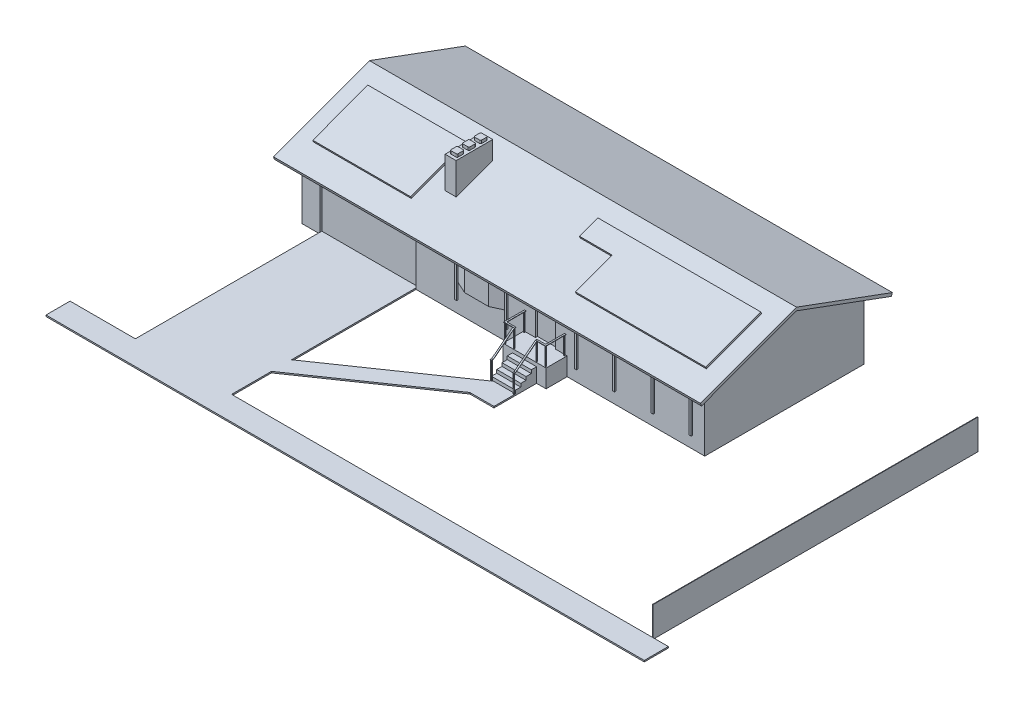
SolidWorks part; units mm, degrees
ref_plane "Front Plane" through (0, 0, 0) normal (0, 0, 1) x (1, 0, 0)
ref_plane "Top Plane" through (0, 0, 0) normal (0, 1, 0) x (1, 0, 0)
ref_plane "Right Plane" through (0, 0, 0) normal (1, 0, 0) x (0, 0, -1)
sketch "Sketch1" plane through (0, 0, 0) normal (0, 1, 0) x (1, 0, 0)
  line L1 (-10210.8, -4038.6) -> (10210.8, -4038.6)
  line L2 (-10210.8, -4038.6) -> (-10210.8, 4038.6)
  line L3 (-10210.8, 4038.6) -> (10210.8, 4038.6)
  line L4 (10210.8, -4038.6) -> (10210.8, 4038.6)
  line L5 (-10210.8, -4038.6) -> (10210.8, 4038.6) construction
  line L6 (-10210.8, 4038.6) -> (10210.8, -4038.6) construction
  point P0 (0, 0)
  dimension "D1" = 20421.6
  dimension "D2" = 8077.2
extrude "Boss-Extrude1" add sketch "Sketch1" along normal blind 3175
sketch "Sketch2" plane through (10210.8, 0, 0) normal (1, 0, 0) x (0, 0, -1)
  line L0 (-4809.5683, 2891.0202) -> (-4038.6, 3175)
  line L1 (4038.6, 3175) -> (4809.5683, 2891.0202)
  line L6 (-4862.2438, 3034.0274) -> (0, 4824.9946)
  line L7 (0, 4824.9946) -> (4862.2438, 3034.0274)
  line L8 (-4809.5683, 2891.0202) -> (-4862.2438, 3034.0274)
  line L9 (4809.5683, 2891.0202) -> (4862.2438, 3034.0274)
  line L10 (0, 0) -> (0, 7136.8719) construction
  line L11 (-4038.6, 3175) -> (4038.6, 3175)
  line L12 (-4038.6, 3175) -> (-4038.6, 0) construction
  line L13 (4038.6, 3175) -> (4038.6, 0) construction
  point P1 (0, 5113.5377)
  point P2 (0, 5113.5377)
  point P4 (0, 5113.5377)
  point P7 (0, 5189.3875)
  dimension "D1" = 5181.6
  dimension "D2" = 770.9683
  dimension "D3" = 770.9683
  dimension "D4" = 152.4
  dimension "D5" = 5181.6
  dimension "D6" = 152.4
extrude "Boss-Extrude2" add sketch "Sketch2" against normal up to surface (20421.6 mm away) up to face at (-10210.8, 1587.5, 0)
sketch "Sketch3" plane through (10210.8, 0, 0) normal (1, 0, 0) x (0, 0, -1)
  line L0 (-4862.2438, 3034.0274) -> (-4809.5683, 2891.0202)
  line L1 (-4809.5683, 2891.0202) -> (0, 4662.5849)
  line L2 (0, 4662.5849) -> (4809.5683, 2891.0202)
  line L3 (4809.5683, 2891.0202) -> (4862.2438, 3034.0274)
  line L4 (4862.2438, 3034.0274) -> (0, 4824.9946)
  line L5 (0, 4824.9946) -> (-4862.2438, 3034.0274)
extrude "Boss-Extrude3" add sketch "Sketch3" along normal blind 609.6
sketch "Sketch4" plane through (-10210.8, 0, 0) normal (-1, 0, 0) x (0, 0, 1)
  line L0 (-4862.2438, 3034.0274) -> (0, 4824.9946)
  line L1 (0, 4824.9946) -> (4862.2438, 3034.0274)
  line L2 (4862.2438, 3034.0274) -> (4809.5683, 2891.0202)
  line L3 (4809.5683, 2891.0202) -> (0, 4662.5849)
  line L4 (0, 4662.5849) -> (-4809.5683, 2891.0202)
  line L5 (-4809.5683, 2891.0202) -> (-4862.2438, 3034.0274)
extrude "Boss-Extrude4" add sketch "Sketch4" along normal blind 609.6
sketch "Sketch7" plane through (0, 0, 0) normal (0, 1, 0) x (1, 0, 0)
  line L0 (-10820.4, -4862.2438) -> (-10820.4, 0) construction
  line L1 (-4216.4, -914.4) -> (-3657.6, -914.4)
  line L2 (-4216.4, -914.4) -> (-4216.4, -2768.6)
  line L3 (-4216.4, -2768.6) -> (-3657.6, -2768.6)
  line L4 (-3657.6, -914.4) -> (-3657.6, -2768.6)
  line L5 (-10820.4, 0) -> (10820.4, 0) construction
  dimension "D1" = 6604
  dimension "D2" = 558.8
  dimension "D3" = 1854.2
  dimension "D4" = 914.4
extrude "Boss-Extrude5" add sketch "Sketch7" along normal blind 6165.342
sketch "Sketch8" plane through (-3657.6, 0, 0) normal (1, 0, 0) x (0, 0, -1)
  line L0 (-2768.6, 6165.342) -> (-914.4, 6165.342)
  line L1 (-914.4, 6165.342) -> (-914.4, 5402.5829)
  line L2 (-914.4, 6165.342) -> (-914.4, 4488.1829) construction
  line L3 (-914.4, 5402.5829) -> (-2768.6, 5402.5829)
  line L4 (-2768.6, 6165.342) -> (-2768.6, 3805.2037) construction
  line L5 (-2768.6, 5402.5829) -> (-2768.6, 6165.342)
  dimension "D1" = 914.4
extrude "Cut-Extrude1" cut sketch "Sketch8" against normal up to next
sketch "Sketch9" plane through (0, 4248.5676, 1564.9247) normal (0, 0.9384, 0.3456) x (1, 0, 0)
  line L0 (-8356.6, 753.3102) -> (-8356.6, -237.2898)
  line L1 (-10007.6, 753.3102) -> (-8356.6, 753.3102)
  line L2 (-10007.6, 753.3102) -> (-10007.6, -237.2898)
  line L3 (-10007.6, -237.2898) -> (-8356.6, -237.2898)
  line L4 (-8356.6, 753.3102) -> (-8356.6, -237.2898)
  line L5 (-8356.6, 753.3102) -> (-6705.6, 753.3102)
  line L6 (-6705.6, 753.3102) -> (-6705.6, -237.2898)
  line L7 (-8356.6, -237.2898) -> (-6705.6, -237.2898)
  line L8 (-6705.6, 753.3102) -> (-6705.6, -237.2898)
  line L9 (-6705.6, 753.3102) -> (-5054.6, 753.3102)
  line L10 (-5054.6, 753.3102) -> (-5054.6, -237.2898)
  line L11 (-6705.6, -237.2898) -> (-5054.6, -237.2898)
  line L12 (-8356.6, -237.2898) -> (-8356.6, -1227.8898)
  line L13 (-8356.6, -237.2898) -> (-6705.6, -237.2898)
  line L14 (-6705.6, -237.2898) -> (-6705.6, -1227.8898)
  line L15 (-8356.6, -1227.8898) -> (-6705.6, -1227.8898)
  line L16 (-6705.6, -237.2898) -> (-6705.6, -1227.8898)
  line L17 (-6705.6, -237.2898) -> (-5054.6, -237.2898)
  line L18 (-5054.6, -237.2898) -> (-5054.6, -1227.8898)
  line L19 (-6705.6, -1227.8898) -> (-5054.6, -1227.8898)
  line L20 (-8356.6, -1227.8898) -> (-8356.6, -2218.4898)
  line L21 (-8356.6, -1227.8898) -> (-6705.6, -1227.8898)
  line L22 (-6705.6, -1227.8898) -> (-6705.6, -2218.4898)
  line L23 (-8356.6, -2218.4898) -> (-6705.6, -2218.4898)
  line L24 (-6705.6, -1227.8898) -> (-6705.6, -2218.4898)
  line L25 (-6705.6, -1227.8898) -> (-5054.6, -1227.8898)
  line L26 (-5054.6, -1227.8898) -> (-5054.6, -2218.4898)
  line L27 (-6705.6, -2218.4898) -> (-5054.6, -2218.4898)
  line L28 (-10007.6, -237.2898) -> (-10007.6, -1227.8898)
  line L29 (-10007.6, -237.2898) -> (-8356.6, -237.2898)
  line L30 (-8356.6, -237.2898) -> (-8356.6, -1227.8898)
  line L31 (-10007.6, -1227.8898) -> (-8356.6, -1227.8898)
  line L32 (-10007.6, -1227.8898) -> (-10007.6, -2218.4898)
  line L33 (-10007.6, -1227.8898) -> (-8356.6, -1227.8898)
  line L34 (-8356.6, -1227.8898) -> (-8356.6, -2218.4898)
  line L35 (-10007.6, -2218.4898) -> (-8356.6, -2218.4898)
  line L36 (-10820.4, -3513.8898) -> (-10820.4, 1667.7102) construction
  line L37 (-10820.4, 1667.7102) -> (10820.4, 1667.7102) construction
  line L38 (6604, 753.3102) -> (6604, -237.2898)
  line L39 (8255, 753.3102) -> (9906, 753.3102)
  line L40 (8255, 753.3102) -> (8255, -237.2898)
  line L41 (8255, -237.2898) -> (9906, -237.2898)
  line L42 (9906, 753.3102) -> (9906, -237.2898)
  line L43 (6604, 753.3102) -> (8255, 753.3102)
  line L44 (8255, 753.3102) -> (8255, -237.2898)
  line L45 (6604, -237.2898) -> (8255, -237.2898)
  line L46 (4953, 753.3102) -> (4953, -237.2898)
  line L47 (4953, 753.3102) -> (6604, 753.3102)
  line L48 (6604, 753.3102) -> (6604, -237.2898)
  line L49 (4953, -237.2898) -> (6604, -237.2898)
  line L50 (3302, 753.3102) -> (3302, -237.2898)
  line L51 (3302, 753.3102) -> (4953, 753.3102)
  line L52 (4953, 753.3102) -> (4953, -237.2898)
  line L53 (3302, -237.2898) -> (4953, -237.2898)
  line L54 (6604, -237.2898) -> (6604, -1227.8898)
  line L55 (6604, -237.2898) -> (8255, -237.2898)
  line L56 (8255, -237.2898) -> (8255, -1227.8898)
  line L57 (6604, -1227.8898) -> (8255, -1227.8898)
  line L58 (4953, -237.2898) -> (4953, -1227.8898)
  line L59 (4953, -237.2898) -> (6604, -237.2898)
  line L60 (6604, -237.2898) -> (6604, -1227.8898)
  line L61 (4953, -1227.8898) -> (6604, -1227.8898)
  line L62 (3302, -237.2898) -> (3302, -1227.8898)
  line L63 (3302, -237.2898) -> (4953, -237.2898)
  line L64 (4953, -237.2898) -> (4953, -1227.8898)
  line L65 (3302, -1227.8898) -> (4953, -1227.8898)
  line L66 (6604, -1227.8898) -> (6604, -2218.4898)
  line L67 (6604, -1227.8898) -> (8255, -1227.8898)
  line L68 (8255, -1227.8898) -> (8255, -2218.4898)
  line L69 (6604, -2218.4898) -> (8255, -2218.4898)
  line L70 (4953, -1227.8898) -> (4953, -2218.4898)
  line L71 (4953, -1227.8898) -> (6604, -1227.8898)
  line L72 (6604, -1227.8898) -> (6604, -2218.4898)
  line L73 (4953, -2218.4898) -> (6604, -2218.4898)
  line L74 (3302, -1227.8898) -> (3302, -2218.4898)
  line L75 (3302, -1227.8898) -> (4953, -1227.8898)
  line L76 (4953, -1227.8898) -> (4953, -2218.4898)
  line L77 (3302, -2218.4898) -> (4953, -2218.4898)
  line L78 (8255, -237.2898) -> (8255, -1227.8898)
  line L79 (8255, -237.2898) -> (9906, -237.2898)
  line L80 (9906, -237.2898) -> (9906, -1227.8898)
  line L81 (8255, -1227.8898) -> (9906, -1227.8898)
  line L82 (8255, -1227.8898) -> (8255, -2218.4898)
  line L83 (8255, -1227.8898) -> (9906, -1227.8898)
  line L84 (9906, -1227.8898) -> (9906, -2218.4898)
  line L85 (8255, -2218.4898) -> (9906, -2218.4898)
  line L86 (10820.4, 1667.7102) -> (10820.4, -3513.8898) construction
  line L88 (3302, 753.3102) -> (1651, 753.3102)
  line L89 (3302, 753.3102) -> (3302, -237.2898)
  line L90 (3302, -237.2898) -> (1651, -237.2898)
  line L91 (1651, 753.3102) -> (1651, -237.2898)
  dimension "D1" = 1651
  dimension "D2" = 990.6
  dimension "D5" = 812.8
  dimension "D6" = 914.4
  dimension "D7" = 990.6
  dimension "D8" = 1651
  dimension "D11" = 914.4
  dimension "D12" = 914.4
  dimension "D13" = 1651
  dimension "D3" = 3
  dimension "D4" = 3
  dimension "D9" = 4
  dimension "D10" = 3
extrude "Boss-Extrude6" add sketch "Sketch9" along direction (0, 0.9384, 0.3456) on the side of the normal blind 101.6 contours L2 L3 L0 L1 | L0 L7 L6 L5 | L6 L11 L10 L9 | L28 L31 L12 L3 | L12 L15 L14 L7 | L14 L19 L18 L11 | L32 L35 L20 L31 | L20 L23 L22 L15 | L22 L27 L26 L19 | L88 L91 L90 L50 | L50 L53 L46 L51 | L62 L65 L58 L53 | L74 L77 L70 L65 | L70 L73 L66 L61 | L58 L61 L54 L49 | L46 L49 L38 L47 | L38 L45 L40 L43 | L54 L57 L56 L45 | L66 L69 L68 L57 | L68 L85 L84 L81 | L56 L81 L80 L41 | L42 L39 L40 L41 region at (-7531.1, 4337.7462, 1322.8163) region at (-9182.1, 4337.7462, 1322.8163) region at (-9182.1, 3995.3554, 2252.3629) region at (-7531.1, 3995.3554, 2252.3629) region at (-5880.1, 4337.7462, 1322.8163) region at (-5880.1, 3995.3554, 2252.3629) region at (-7531.1, 3652.9646, 3181.9096) region at (-9182.1, 3652.9646, 3181.9096) region at (-5880.1, 3652.9646, 3181.9096) region at (7429.5, 4337.7462, 1322.8163) region at (5778.5, 4337.7462, 1322.8163) region at (5778.5, 3995.3554, 2252.3629) region at (7429.5, 3995.3554, 2252.3629) region at (9080.5, 4337.7462, 1322.8163) region at (4127.5, 4337.7462, 1322.8163) region at (9080.5, 3995.3554, 2252.3629) region at (4127.5, 3995.3554, 2252.3629) region at (5778.5, 3652.9646, 3181.9096) region at (7429.5, 3652.9646, 3181.9096) region at (2476.5, 4337.7462, 1322.8163) region at (9080.5, 3652.9646, 3181.9096) region at (4127.5, 3652.9646, 3181.9096)
sketch "Sketch10" plane through (0, 0, 4038.6) normal (0, 0, 1) x (1, 0, 0)
  line L0 (-10210.8, 0) -> (10210.8, 0) construction
  line L1 (-9296.4, 0) -> (-4419.6, 0)
  line L2 (-9296.4, 0) -> (-9296.4, 2438.4)
  line L3 (-9296.4, 2438.4) -> (-4419.6, 2438.4)
  line L4 (-4419.6, 0) -> (-4419.6, 2438.4)
  line L5 (-10210.8, 3175) -> (-10210.8, 0) construction
  line L6 (-2286, 1371.6) -> (152.4, 1371.6)
  line L7 (-2286, 1371.6) -> (-2286, 3175)
  line L8 (-2286, 3175) -> (152.4, 3175)
  line L9 (152.4, 1371.6) -> (152.4, 3175)
  line L10 (1054.1, 914.4) -> (3238.5, 914.4)
  line L11 (1054.1, 914.4) -> (1054.1, 0)
  line L12 (1054.1, 0) -> (3238.5, 0)
  line L13 (3238.5, 914.4) -> (3238.5, 0)
  line L14 (1638.3, 2971.8) -> (2654.3, 2971.8)
  line L15 (1638.3, 2971.8) -> (1638.3, 914.4)
  line L16 (1638.3, 914.4) -> (2654.3, 914.4)
  line L17 (2654.3, 2971.8) -> (2654.3, 914.4)
  line L18 (3784.6, 2997.2) -> (5613.4, 2997.2)
  line L19 (3784.6, 2997.2) -> (3784.6, 2133.6)
  line L20 (3784.6, 2133.6) -> (5613.4, 2133.6)
  line L21 (5613.4, 2997.2) -> (5613.4, 2133.6)
  line L22 (7670.8, 2997.2) -> (9499.6, 2997.2)
  line L23 (7670.8, 2997.2) -> (7670.8, 2133.6)
  line L24 (7670.8, 2133.6) -> (9499.6, 2133.6)
  line L25 (9499.6, 2997.2) -> (9499.6, 2133.6)
  line L26 (10210.8, 3175) -> (10210.8, 0) construction
  line L27 (-10210.8, 3175) -> (10210.8, 3175) construction
  point P30 (2146.3, 914.4)
  point P31 (2146.3, 914.4)
  line M23 (-10210.8, 0) -> (10210.8, 0)
  line M25 (10210.8, 3175) -> (-10210.8, 3175)
  dimension "D1" = 914.4
  dimension "D2" = 4876.8
  dimension "D3" = 2438.4
  dimension "D4" = 2133.6
  dimension "D5" = 711.2
  dimension "D6" = 1828.8
  dimension "D7" = 2057.4
  dimension "D8" = 1828.8
  dimension "D9" = 546.1
  dimension "D10" = 2184.4
  dimension "D11" = 1016
  dimension "D12" = 914.4
  dimension "D13" = 2057.4
  dimension "D14" = 863.6
  dimension "D15" = 863.6
  dimension "D16" = 2133.6
  dimension "D17" = 2133.6
  dimension "D18" = 1371.6
  dimension "D19" = 2438.4
extrude "Cut-Extrude2" cut sketch "Sketch10" against normal blind 101.6 contours L4 L3 L2 M23 | L21 L18 L19 L20 | L25 L22 L23 L24 region at (-6858, 1219.2, 4038.6) region at (4699, 2565.4, 4038.6) region at (8585.2, 2565.4, 4038.6)
extrude "Boss-Extrude7" add sketch "Sketch10<3>" along normal blind 1066.8 contours L13 L10 L11 M23 region at (2146.3, 457.2, 4038.6)
sketch "Sketch10<3>" plane through (0, 0, 4038.6) normal (0, 0, 1) x (1, 0, 0) same geometry as "Sketch10"
extrude "Boss-Extrude8" add sketch "Sketch10<4>" along normal blind 279.4 contours L6 L9 L7 M25 region at (-1066.8, 2273.3, 4038.6)
sketch "Sketch10<4>" plane through (0, 0, 4038.6) normal (0, 0, 1) x (1, 0, 0) same geometry as "Sketch10"
sketch "Sketch11" plane through (0, 1371.6, 0) normal (0, -1, 0) x (1, 0, 0)
  line L0 (-1676.4, 4318) -> (-2286, 4038.6)
  line L1 (-2286, 4318) -> (152.4, 4318) construction
  line L2 (-2286, 4318) -> (-2286, 4038.6) construction
  line L3 (-2286, 4038.6) -> (-2286, 4318)
  line L4 (-2286, 4318) -> (-1676.4, 4318)
  line L10 (152.4, 4038.6) -> (-457.2, 4318)
  line L11 (-457.2, 4318) -> (152.4, 4318)
  line L12 (152.4, 4318) -> (152.4, 4038.6)
  line L13 (-1066.8, 4318) -> (-1066.8, 3614.0331) construction
  line L15 (152.4, 4318) -> (-2286, 4318) construction
  point P15 (-1066.8, 4318)
  point P16 (-1066.8, 4318)
  dimension "D1" = 1219.2
  dimension "D2" = 609.6
extrude "Cut-Extrude3" cut sketch "Sketch11" against normal up to surface (1700.4853 mm away) up to face at (-355.6, 3606.3792, 2867.4614)
extrude "Cut-Extrude4" cut sketch "Sketch10<5>" against normal blind 101.6 contours L17 L14 L15 L10 region at (2146.3, 1943.1, 4038.6)
sketch "Sketch10<5>" plane through (0, 0, 4038.6) normal (0, 0, 1) x (1, 0, 0) same geometry as "Sketch10"
sketch "Sketch12" plane through (0, 0, 5105.4) normal (0, 0, 1) x (1, 0, 0)
  line L0 (1054.1, 0) -> (3238.5, 0) construction
  line L1 (1536.7, 0) -> (2755.9, 0)
  line L2 (1536.7, 0) -> (1536.7, 730.25)
  line L3 (1536.7, 730.25) -> (2755.9, 730.25)
  line L4 (2755.9, 0) -> (2755.9, 730.25)
  line L5 (2146.3, -952.0203) -> (2146.3, 3746.1665) construction
  line L6 (1054.1, 914.4) -> (3238.5, 914.4) construction
  line L7 (1638.3, 914.4) -> (2654.3, 914.4) construction
  point P8 (2146.3, 730.25)
  point P11 (2146.3, 914.4)
  dimension "D1" = 1219.2
  dimension "D2" = 184.15
extrude "Boss-Extrude9" add sketch "Sketch12" along normal blind 1066.8
sketch "Sketch13" plane through (2755.9, 0, 0) normal (1, 0, 0) x (0, 0, -1)
  line L0 (-5372.1, 730.25) -> (-5372.1, 565.15)
  line L1 (-6172.2, 730.25) -> (-5105.4, 730.25) construction
  line L2 (-5372.1, 565.15) -> (-5638.8, 565.15)
  line L3 (-5638.8, 565.15) -> (-5638.8, 400.05)
  line L4 (-5638.8, 400.05) -> (-5905.5, 400.05)
  line L5 (-5905.5, 400.05) -> (-5905.5, 234.95)
  line L6 (-5905.5, 234.95) -> (-6172.2, 234.95)
  line L7 (-6172.2, 0) -> (-6172.2, 730.25) construction
  line L8 (-6172.2, 234.95) -> (-6172.2, 730.25)
  line L9 (-6172.2, 730.25) -> (-5372.1, 730.25)
  line L10 (-5105.4, 0) -> (-5105.4, 730.25) construction
  line L11 (-6172.2, 0) -> (-5105.4, 0) construction
  dimension "D1" = 266.7
  dimension "D2" = 266.7
  dimension "D3" = 266.7
  dimension "D4" = 165.1
  dimension "D5" = 165.1
  dimension "D6" = 165.1
  dimension "D7" = 234.95
extrude "Cut-Extrude5" cut sketch "Sketch13" against normal up to next
sketch "Sketch14" plane through (0, 0, 6172.2) normal (0, 0, 1) x (1, 0, 0)
  line L0 (1536.7, 234.95) -> (1536.7, 0) construction
  line L5 (1536.7, 0) -> (2755.9, 0)
  line L6 (1536.7, 0) -> (1536.7, 69.85)
  line L7 (1536.7, 69.85) -> (2755.9, 69.85)
  line L8 (2755.9, 0) -> (2755.9, 69.85)
  line L9 (2755.9, 0) -> (2755.9, 234.95) construction
  line L10 (1536.7, 234.95) -> (2755.9, 234.95) construction
  dimension "D1" = 165.1
extrude "Boss-Extrude10" add sketch "Sketch14" along normal blind 1092.2
sketch "Sketch15" plane through (0, 0, 3937) normal (0, 0, 1) x (1, 0, 0)
  line L0 (-4419.6, 0) -> (-4419.6, 2438.4) construction
  line L1 (-9296.4, 0) -> (-4419.6, 0)
  line L2 (-9296.4, 0) -> (-9296.4, 69.85)
  line L3 (-9296.4, 69.85) -> (-4419.6, 69.85)
  line L4 (-4419.6, 0) -> (-4419.6, 69.85)
  dimension "D1" = 69.85
extrude "Boss-Extrude11" add sketch "Sketch15" along normal blind 9448.8
sketch "Sketch16" plane through (0, 0, 0) normal (0, 1, 0) x (1, 0, 0)
  line L0 (1536.7, -7264.4) -> (-4419.6, -11364.6438)
  line L1 (-4419.6, -13385.8) -> (-4419.6, -4038.6) construction
  line L2 (-4419.6, -11364.6438) -> (-4419.6, -10348.6438)
  line L3 (-4419.6, -10348.6438) -> (1536.7, -6248.4)
  line L4 (1536.7, -6248.4) -> (1536.7, -7264.4)
  line L5 (-10820.4, -4862.2438) -> (10820.4, -4862.2438) construction
  point P10 (0, 0)
  point P11 (1536.7, -6375.7175)
  dimension "D1" = 5486.4
  dimension "D2" = 1016
  dimension "D3" = 1016
extrude "Boss-Extrude12" add sketch "Sketch16" along normal blind 69.85
sketch "Sketch17" plane through (0, 0, 13385.8) normal (0, 0, 1) x (1, 0, 0)
  line L0 (-4419.6, 69.85) -> (-9296.4, 69.85) construction
  line L1 (-12605.8014, 0) -> (17713.7666, 0)
  line L2 (-12605.8014, 0) -> (-12605.8014, 69.85)
  line L3 (-12605.8014, 69.85) -> (17713.7666, 69.85)
  line L4 (17713.7666, 0) -> (17713.7666, 69.85)
  line L5 (-9296.4, 0) -> (-4419.6, 0) construction
extrude "Boss-Extrude13" add sketch "Sketch17" along normal blind 1219.2
sketch "Sketch18" plane through (0, 0, 4038.6) normal (0, 0, 1) x (1, 0, 0)
  line L0 (3784.6, 2997.2) -> (3784.6, 2133.6) construction
  line L1 (3683, 609.6) -> (3784.6, 609.6)
  line L2 (3683, 609.6) -> (3683, 3175)
  line L3 (3683, 3175) -> (3784.6, 3175)
  line L4 (3784.6, 609.6) -> (3784.6, 3175)
  line L5 (5613.4, 609.6) -> (5715, 609.6)
  line L6 (5613.4, 609.6) -> (5613.4, 3175)
  line L7 (5613.4, 3175) -> (5715, 3175)
  line L8 (5715, 609.6) -> (5715, 3175)
  line L9 (7569.2, 609.6) -> (7670.8, 609.6)
  line L10 (7569.2, 609.6) -> (7569.2, 3175)
  line L11 (7569.2, 3175) -> (7670.8, 3175)
  line L12 (7670.8, 609.6) -> (7670.8, 3175)
  line L13 (9499.6, 609.6) -> (9601.2, 609.6)
  line L14 (9499.6, 609.6) -> (9499.6, 3175)
  line L15 (9499.6, 3175) -> (9601.2, 3175)
  line L16 (9601.2, 609.6) -> (9601.2, 3175)
  line L17 (5613.4, 2997.2) -> (5613.4, 2133.6) construction
  line L18 (7670.8, 2997.2) -> (7670.8, 2133.6) construction
  line L19 (9499.6, 2997.2) -> (9499.6, 2133.6) construction
  line L20 (3238.5, 0) -> (10210.8, 0) construction
  line L21 (152.4, 3175) -> (10210.8, 3175) construction
  line L22 (-10210.8, 3175) -> (-2286, 3175) construction
  line L23 (-2387.6, 3175) -> (-2286, 3175)
  line L24 (-2387.6, 3175) -> (-2387.6, 609.6)
  line L25 (-2387.6, 609.6) -> (-2286, 609.6)
  line L26 (-2286, 3175) -> (-2286, 609.6)
  line L27 (152.4, 3175) -> (254, 3175)
  line L28 (152.4, 3175) -> (152.4, 609.6)
  line L29 (152.4, 609.6) -> (254, 609.6)
  line L30 (254, 3175) -> (254, 609.6)
  line L31 (-2286, 1371.6) -> (-2286, 3175) construction
  line L32 (152.4, 1371.6) -> (152.4, 3175) construction
  dimension "D1" = 101.6
  dimension "D2" = 609.6
extrude "Boss-Extrude14" add sketch "Sketch18" along normal blind 76.2
sketch "Sketch19" plane through (0, 914.4, 0) normal (0, 1, 0) x (1, 0, 0)
  line L0 (1054.1, -5105.4) -> (3238.5, -5105.4) construction
  line L1 (1092.2, -5067.3) -> (1130.3, -5067.3)
  line L2 (1092.2, -5067.3) -> (1092.2, -5029.2)
  line L3 (1092.2, -5029.2) -> (1130.3, -5029.2)
  line L4 (1130.3, -5067.3) -> (1130.3, -5029.2)
  line L5 (3176.5995, -5067.3) -> (3138.4995, -5067.3)
  line L6 (3176.5995, -5067.3) -> (3176.5995, -5029.2)
  line L7 (3176.5995, -5029.2) -> (3138.4995, -5029.2)
  line L8 (3138.4995, -5067.3) -> (3138.4995, -5029.2)
  line L9 (3138.4995, -4076.7) -> (3176.5995, -4076.7)
  line L10 (3138.4995, -4076.7) -> (3138.4995, -4114.8)
  line L11 (3138.4995, -4114.8) -> (3176.5995, -4114.8)
  line L12 (3176.5995, -4076.7) -> (3176.5995, -4114.8)
  line L13 (1092.2, -4076.7) -> (1130.3, -4076.7)
  line L14 (1092.2, -4076.7) -> (1092.2, -4114.8)
  line L15 (1092.2, -4114.8) -> (1130.3, -4114.8)
  line L16 (1130.3, -4076.7) -> (1130.3, -4114.8)
  line L17 (1557.7366, -5029.2) -> (1595.8366, -5029.2)
  line L18 (1557.7366, -5029.2) -> (1557.7366, -5067.3)
  line L19 (1557.7366, -5067.3) -> (1595.8366, -5067.3)
  line L20 (1595.8366, -5029.2) -> (1595.8366, -5067.3)
  line L21 (2734.3851, -5067.3) -> (2696.2851, -5067.3)
  line L22 (2734.3851, -5067.3) -> (2734.3851, -5029.2)
  line L23 (2734.3851, -5029.2) -> (2696.2851, -5029.2)
  line L24 (2696.2851, -5067.3) -> (2696.2851, -5029.2)
  line L25 (1054.1, -5105.4) -> (1054.1, -4038.6) construction
  line L26 (1054.1, -4038.6) -> (1638.3, -4038.6) construction
  dimension "D1" = 38.1
  dimension "D2" = 38.1
  dimension "D3" = 38.1
  dimension "D4" = 38.1
  dimension "D5" = 38.1
  dimension "D6" = 38.1
  dimension "D7" = 38.1
extrude "Boss-Extrude15" add sketch "Sketch19" along normal blind 914.4
sketch "Sketch20" plane through (0, 1828.8, 0) normal (0, 1, 0) x (1, 0, 0)
  line L0 (1130.3, -4114.8) -> (1130.3, -4076.7) construction
  line L1 (1073.15, -4022.2988) -> (1149.35, -4022.2988)
  line L2 (1073.15, -4022.2988) -> (1073.15, -5086.35)
  line L3 (1073.15, -5086.35) -> (1149.35, -5086.35)
  line L4 (1149.35, -4022.2988) -> (1149.35, -5086.35)
  line L5 (1149.35, -5086.35) -> (1614.8866, -5086.35)
  line L6 (1149.35, -5086.35) -> (1149.35, -5010.15)
  line L7 (1149.35, -5010.15) -> (1614.8866, -5010.15)
  line L8 (1614.8866, -5086.35) -> (1614.8866, -5010.15)
  line L9 (3119.4495, -4057.65) -> (3195.6495, -4057.65)
  line L10 (3119.4495, -4057.65) -> (3119.4495, -5086.35)
  line L11 (3119.4495, -5086.35) -> (3195.6495, -5086.35)
  line L12 (3195.6495, -4057.65) -> (3195.6495, -5086.35)
  line L13 (3119.4495, -5086.35) -> (2677.2351, -5086.35)
  line L14 (3119.4495, -5086.35) -> (3119.4495, -5010.15)
  line L15 (3119.4495, -5010.15) -> (2677.2351, -5010.15)
  line L16 (2677.2351, -5086.35) -> (2677.2351, -5010.15)
  line L17 (1092.2, -5067.3) -> (1130.3, -5067.3) construction
  line L18 (1595.8366, -5067.3) -> (1595.8366, -5029.2) construction
  line L19 (2696.2851, -5029.2) -> (2696.2851, -5067.3) construction
  line L20 (3176.5995, -5067.3) -> (3176.5995, -5029.2) construction
  line L21 (3176.5995, -4076.7) -> (3138.4995, -4076.7) construction
  line L22 (2696.2851, -5067.3) -> (2734.3851, -5067.3) construction
  line M11 (1092.2, -4076.7) -> (1092.2, -4114.8)
  line M12 (1092.2, -4114.8) -> (1130.3, -4114.8)
  line M13 (1130.3, -4114.8) -> (1130.3, -4076.7)
  line M14 (1130.3, -4076.7) -> (1092.2, -4076.7)
  dimension "D1" = 76.2
  dimension "D2" = 76.2
  dimension "D3" = 76.2
  dimension "D4" = 76.2
  dimension "D5" = 19.05
  dimension "D6" = 19.05
  dimension "D7" = 19.05
  dimension "D8" = 19.05
  dimension "D9" = 19.05
  dimension "D10" = 19.05
  dimension "D11" = 19.05
extrude "Boss-Extrude17" add sketch "Sketch20" along normal blind 19.05 contours L4 L1 L2 L3 M11 M14 M13 M12 | L5 L8 L7 L4 | L16 L13 L10 L15 | L12 L9 L10 L11 | M14 M11 M12 M13 region at (1111.25, 1828.8, 4562.6841) region at (1382.1183, 1828.8, 5048.25) region at (3157.5495, 1828.8, 4572) region at (2898.3423, 1828.8, 5048.25) region at (1111.25, 1828.8, 4095.75)
sketch "Sketch21" plane through (0, 69.85, 0) normal (0, 1, 0) x (1, 0, 0)
  line L0 (2734.3851, -5067.3) -> (2734.3851, -5029.2) construction
  line L1 (1557.7366, -6229.35) -> (1595.8366, -6229.35)
  line L2 (1557.7366, -6229.35) -> (1557.7366, -6191.25)
  line L3 (1557.7366, -6191.25) -> (1595.8366, -6191.25)
  line L4 (1595.8366, -6229.35) -> (1595.8366, -6191.25)
  line L5 (2696.2851, -6229.35) -> (2734.3851, -6229.35)
  line L6 (2696.2851, -6229.35) -> (2696.2851, -6191.25)
  line L7 (2696.2851, -6191.25) -> (2734.3851, -6191.25)
  line L8 (2734.3851, -6229.35) -> (2734.3851, -6191.25)
  line L9 (2696.2851, -5029.2) -> (2696.2851, -5067.3) construction
  line L10 (1557.7366, -5029.2) -> (1557.7366, -5067.3) construction
  line L11 (1595.8366, -5067.3) -> (1595.8366, -5029.2) construction
  line L12 (2755.9, -6172.2) -> (1536.7, -6172.2) construction
  dimension "D1" = 38.1
  dimension "D2" = 19.05
extrude "Boss-Extrude18" add sketch "Sketch21" along normal blind 914.4
sketch "Sketch22" plane through (0, 984.25, 0) normal (0, 1, 0) x (1, 0, 0)
  line L0 (1557.7366, -6191.25) -> (1557.7366, -6229.35) construction
  line L1 (1538.6866, -6172.2) -> (1614.8866, -6172.2)
  line L2 (1538.6866, -6172.2) -> (1538.6866, -6248.4)
  line L3 (1538.6866, -6248.4) -> (1614.8866, -6248.4)
  line L4 (1614.8866, -6172.2) -> (1614.8866, -6248.4)
  line L5 (2677.2351, -6172.2) -> (2753.4351, -6172.2)
  line L6 (2677.2351, -6172.2) -> (2677.2351, -6248.4)
  line L7 (2677.2351, -6248.4) -> (2753.4351, -6248.4)
  line L8 (2753.4351, -6172.2) -> (2753.4351, -6248.4)
  line L9 (1557.7366, -6229.35) -> (1595.8366, -6229.35) construction
  line L10 (2734.3851, -6229.35) -> (2734.3851, -6191.25) construction
  dimension "D1" = 76.2
  dimension "D2" = 19.05
  dimension "D3" = 19.05
  dimension "D4" = 19.05
extrude "Boss-Extrude19" add sketch "Sketch22" along normal blind 19.05
sketch "Sketch23" plane through (0, 0, 5086.35) normal (0, 0, 1) x (1, 0, 0)
  line L0 (1073.15, 1847.85) -> (1614.8866, 1847.85) construction
  line L1 (1614.8866, 1828.8) -> (1538.6866, 1828.8)
  line L2 (1614.8866, 1828.8) -> (1614.8866, 1847.85)
  line L3 (1614.8866, 1847.85) -> (1538.6866, 1847.85)
  line L4 (1538.6866, 1828.8) -> (1538.6866, 1847.85)
  line L5 (3195.6495, 1847.85) -> (2677.2351, 1847.85) construction
  line L6 (2677.2351, 1828.8) -> (2753.4351, 1828.8)
  line L7 (2677.2351, 1828.8) -> (2677.2351, 1847.85)
  line L8 (2677.2351, 1847.85) -> (2753.4351, 1847.85)
  line L9 (2753.4351, 1828.8) -> (2753.4351, 1847.85)
  dimension "D1" = 76.2
  dimension "D2" = 76.2
sketch3d "3DSketch1"
  line L0 (1538.6866, 1847.85, 5086.35) -> (1538.6866, 1003.3, 6172.2)
  line L1 (2677.2351, 1847.85, 5086.35) -> (2677.2351, 1003.3, 6172.2)
  line L2 (2753.4351, 1847.85, 5086.35) -> (2753.4351, 1003.3, 6172.2)
loft "Loft1" add section "Sketch23" section face at (1576.7866, 993.775, 6172.2) connector at (1538.6866, 1847.85, 5086.35) connector at (1538.6866, 1003.3, 6172.2)
loft "Loft3" add section face at (2715.3351, 993.775, 6172.2) section "Sketch23<5>" connector at (2753.4351, 984.25, 6172.2) connector at (2753.4351, 1828.8, 5086.35)
sketch "Sketch23<5>" plane through (0, 0, 5086.35) normal (0, 0, 1) x (1, 0, 0) same geometry as "Sketch23"
sketch "Sketch24" plane through (0, 5402.5829, 0) normal (0, 1, 0) x (1, 0, 0)
  line L0 (-3937, -914.4) -> (-3937, -2768.6) construction
  line L1 (-4064, -1066.8) -> (-3810, -1066.8)
  line L2 (-4114.8, -1117.6) -> (-4114.8, -1371.6)
  line L3 (-4064, -1422.4) -> (-3810, -1422.4)
  line L4 (-3759.2, -1117.6) -> (-3759.2, -1371.6)
  line L5 (-4064, -1663.7) -> (-3810, -1663.7)
  line L6 (-4114.8, -1714.5) -> (-4114.8, -1968.5)
  line L7 (-4064, -2019.3) -> (-3810, -2019.3)
  line L8 (-3759.2, -1714.5) -> (-3759.2, -1968.5)
  line L9 (-4064, -2260.6) -> (-3810, -2260.6)
  line L10 (-4114.8, -2311.4) -> (-4114.8, -2565.4)
  line L11 (-4064, -2616.2) -> (-3810, -2616.2)
  line L12 (-3759.2, -2311.4) -> (-3759.2, -2565.4)
  line L13 (-4216.4, -914.4) -> (-3657.6, -914.4) construction
  line L14 (-4216.4, -2768.6) -> (-3657.6, -2768.6) construction
  line L15 (-4609.6328, -1841.5) -> (-3072.9217, -1841.5) construction
  arc A0 (-3810, -2616.2) -> (-3759.2, -2565.4) centre (-3810, -2565.4) ccw
  arc A1 (-4114.8, -2565.4) -> (-4064, -2616.2) centre (-4064, -2565.4) ccw
  arc A2 (-4064, -2260.6) -> (-4114.8, -2311.4) centre (-4064, -2311.4) ccw
  arc A3 (-3810, -2260.6) -> (-3759.2, -2311.4) centre (-3810, -2311.4) cw
  arc A4 (-4114.8, -1968.5) -> (-4064, -2019.3) centre (-4064, -1968.5) ccw
  arc A5 (-3810, -2019.3) -> (-3759.2, -1968.5) centre (-3810, -1968.5) ccw
  arc A6 (-3810, -1663.7) -> (-3759.2, -1714.5) centre (-3810, -1714.5) cw
  arc A7 (-4064, -1663.7) -> (-4114.8, -1714.5) centre (-4064, -1714.5) ccw
  arc A8 (-4114.8, -1371.6) -> (-4064, -1422.4) centre (-4064, -1371.6) ccw
  arc A9 (-3810, -1422.4) -> (-3759.2, -1371.6) centre (-3810, -1371.6) ccw
  arc A10 (-3810, -1066.8) -> (-3759.2, -1117.6) centre (-3810, -1117.6) cw
  arc A11 (-4064, -1066.8) -> (-4114.8, -1117.6) centre (-4064, -1117.6) ccw
  point P18 (-3937, -2616.2)
  point P19 (-3937, -2019.3)
  point P20 (-3937, -1422.4)
  point P23 (-3937, -1841.5)
  point P24 (-3759.2, -1841.5)
  point P27 (-3759.2, -2616.2)
  point P30 (-4114.8, -2616.2)
  point P33 (-4114.8, -2260.6)
  dimension "D5" = 50.8
  dimension "D1" = 355.6
  dimension "D2" = 355.6
  dimension "D3" = 152.4
  dimension "D4" = 152.4
extrude "Boss-Extrude20" add sketch "Sketch24" along normal blind 152.4
sketch "Sketch25" plane through (0, 0, 0) normal (0, 1, 0) x (1, 0, 0)
  line L0 (10210.8, -4038.6) -> (10210.8, 4038.6) construction
  line L1 (16916.4, 3079.953) -> (16941.8, 3079.953)
  line L2 (16916.4, 3079.953) -> (16916.4, -13385.8)
  line L3 (16916.4, -13385.8) -> (16941.8, -13385.8)
  line L4 (16941.8, 3079.953) -> (16941.8, -13385.8)
  line L5 (17713.7666, -13385.8) -> (-4419.6, -13385.8) construction
  point P6 (0, 0)
  dimension "D1" = 25.4
  dimension "D2" = 6705.6
extrude "Boss-Extrude21" add sketch "Sketch25" along normal blind 1524
